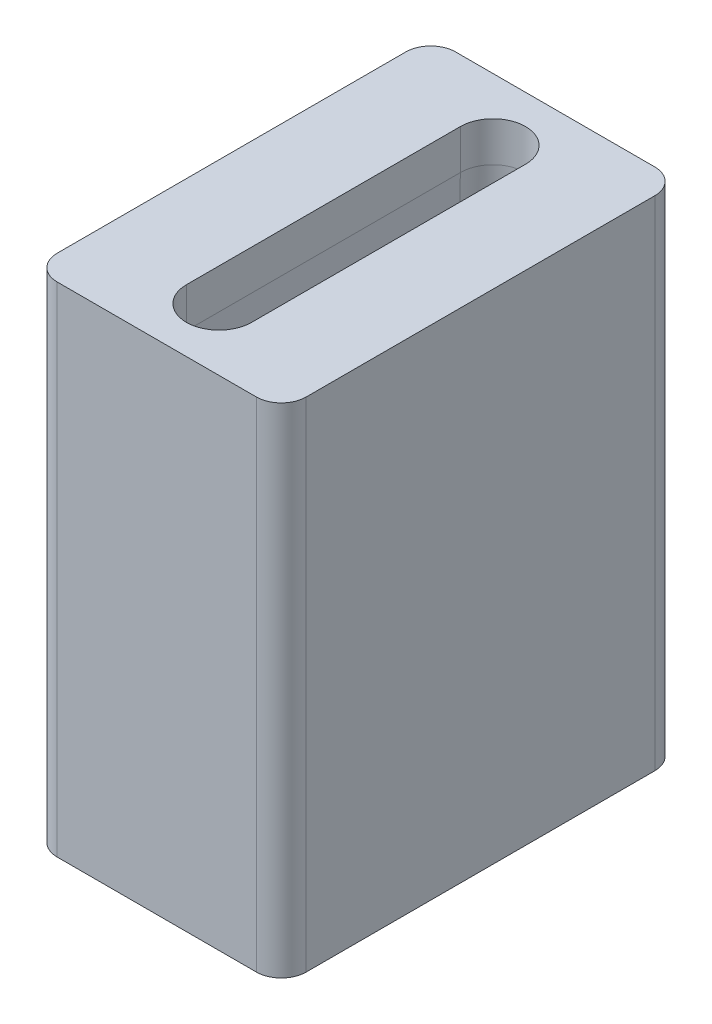
SolidWorks part; units mm, degrees
material "K110"
ref_plane "Front Plane" through (0, 0, 0) normal (0, 0, 1) x (1, 0, 0)
ref_plane "Top Plane" through (0, 0, 0) normal (0, 1, 0) x (1, 0, 0)
ref_plane "Right Plane" through (0, 0, 0) normal (1, 0, 0) x (0, 0, -1)
sketch "Sketch1" plane through (0, 0, 0) normal (0, 1, 0) x (1, 0, 0)
  line L3 (0, -11) -> (0, 11) construction
  line L4 (-2.62, -11) -> (-2.62, 11) construction
  line L5 (2.62, -11) -> (2.62, 11) construction
  line L6 (-8, -16) -> (8, -16)
  line L7 (-10, -14) -> (-10, 14)
  line L8 (-8, 16) -> (8, 16)
  line L9 (10, -14) -> (10, 14)
  line L10 (-10, -16) -> (10, 16) construction
  line L11 (-10, 16) -> (10, -16) construction
  arc A2 (-2.62, -11) -> (2.62, -11) centre (0, -11) ccw construction
  arc A3 (2.62, 11) -> (-2.62, 11) centre (0, 11) ccw construction
  arc A4 (-8, -16) -> (-10, -14) centre (-8, -14) cw
  arc A5 (8, -16) -> (10, -14) centre (8, -14) ccw
  arc A6 (8, 16) -> (10, 14) centre (8, 14) cw
  arc A7 (-10, 14) -> (-8, 16) centre (-8, 14) cw
  point P0 (0, 0)
  point P10 (0, 0)
  dimension "D1" = 22
  dimension "D3" = 2.62
  dimension "D5" = 2
  dimension "D2" = 32
  dimension "D4" = 20
extrude "Boss-Extrude1" add sketch "Sketch1" against normal blind 40
sketch "Sketch5" plane through (0, 0, 0) normal (0, 1, 0) x (1, 0, 0)
  line L0 (0, -11) -> (0, 11) construction
  line L1 (-2.62, -11) -> (-2.62, 11)
  line L2 (2.62, -11) -> (2.62, 11)
  arc A0 (-2.62, -11) -> (2.62, -11) centre (0, -11) ccw
  arc A1 (2.62, 11) -> (-2.62, 11) centre (0, 11) ccw
  point P4 (0, 0)
extrude "Cut-Extrude2" cut sketch "Sketch5" against normal up to next
sketch "Sketch7" plane through (0, 0, 0) normal (0, 0, 1) x (1, 0, 0)
  line L0 (2.62, -3.2) -> (3.2623, -40)
  line L1 (2.62, -40) -> (2.62, 0) construction
  line L2 (-8, -40) -> (8, -40) construction
  line L3 (3.2623, -40) -> (2.62, -40)
  line L4 (2.62, -40) -> (2.62, -3.2)
  line L5 (10, 0) -> (8, 0) construction
  dimension "D1" = 3.2
  dimension "D2" = 1
sketch "Sketch8" plane through (0, 0, 0) normal (0, 1, 0) x (1, 0, 0)
  line L0 (-2.62, 11) -> (-2.62, -11) construction
  line L1 (2.62, -11) -> (2.62, 11) construction
  line L2 (-2.62, 11) -> (-2.62, -11)
  line L3 (2.62, -11) -> (2.62, 11)
  arc A0 (2.62, 11) -> (-2.62, 11) centre (0, 11) ccw construction
  arc A1 (-2.62, -11) -> (2.62, -11) centre (0, -11) ccw construction
  arc A2 (2.62, 11) -> (-2.62, 11) centre (0, 11) ccw
  arc A3 (-2.62, -11) -> (2.62, -11) centre (0, -11) ccw
sweep "Cut-Sweep1" cut profiles "Sketch7" path "Sketch8"
hole_wizard "M3 Tapped Hole1" positions "Sketch11" profile "Sketch10" tap size "M3" standard "ISO"
sketch "Sketch11" plane through (0, -40, 0) normal (0, -1, 0) x (-1, 0, 0)
  line L0 (-8, 16) -> (8, 16) construction
  line L1 (-10, -14) -> (-10, 14) construction
  line L4 (10, 14) -> (10, -14) construction
  line L5 (8, -16) -> (-8, -16) construction
  point P0 (-7, 13)
  point P2 (7, -13)
  dimension "D1" = 3
  dimension "D2" = 3
  dimension "D3" = 3
  dimension "D4" = 3
sketch "Sketch10" plane through (7, -40, -13) normal (1, 0, 0) x (0, 0, -1)
  line L0 (0, 0) -> (0, 9.2511)
  line L1 (0, 9.2511) -> (1.25, 8.5)
  line L2 (1.25, 8.5) -> (1.25, 0.275)
  line L3 (1.25, 0.275) -> (1.525, 0)
  line L5 (1.525, 0) -> (0, 0)
  line L6 (-1.25, 0.275) -> (-1.525, 0) construction
  line L10 (0, 9.2511) -> (-1.25, 8.5) construction
  line L11 (0, -6.35) -> (0, 107.95) construction
  dimension "Tap Drill Dia." = 2.5
  dimension "Tap Drill Depth" = 8.5
  dimension "Near C'Sink Dia." = 3.05
  dimension "Near C'Sink Angle" = 90
  dimension "Drill Angle" = 118
cosmetic thread "Hole Thread1"
cosmetic thread "Hole Thread2"
